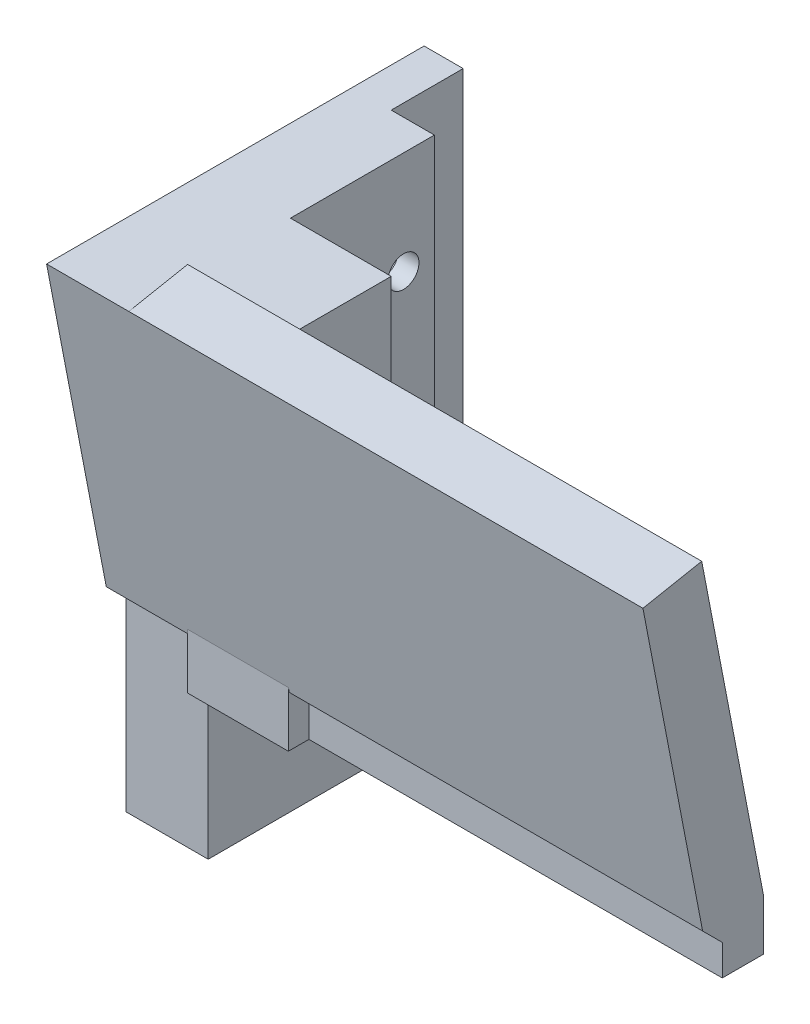
SolidWorks part; units mm, degrees
ref_plane "前视基准面" through (0, 0, 0) normal (0, 0, 1) x (1, 0, 0)
ref_plane "上视基准面" through (0, 0, 0) normal (0, 1, 0) x (1, 0, 0)
ref_plane "右视基准面" through (0, 0, 0) normal (1, 0, 0) x (0, 0, -1)
other "Configuration Table"
sketch "草图1" plane through (0, 0, 0) normal (1, 0, 0) x (0, 0, -1)
  line L0 (0, 0) -> (-10, 0)
  line L1 (-10, 0) -> (-17.7164, 40)
  line L2 (-17.7164, 40) -> (-12, 41.1027)
  line L3 (-12, 41.1027) -> (-6, 10)
  line L4 (-6, 10) -> (0, 10)
  line L5 (0, 10) -> (0, 0)
  dimension "D1" = 10
  dimension "D2" = 6
  dimension "D3" = 10
  dimension "D4" = 6
  dimension "D5" = 40
extrude "凸台-拉伸1" add sketch "草图1" along normal blind 50
sketch "草图2" plane through (0, 0, 0) normal (0, -1, 0) x (1, 0, 0)
  line L4 (0, 10) -> (0, 0)
  line L5 (0, 0) -> (50, 0)
  line L6 (50, 0) -> (50, 10)
  line L7 (50, 10) -> (0, 10)
  line L8 (0, 10) -> (0, 0)
  line L9 (0, 0) -> (50, 0)
  line L10 (50, 0) -> (50, 10)
  line L11 (50, 10) -> (0, 10)
  dimension "D1" = 0
extrude "凸台-拉伸2" add sketch "草图2" along normal blind 10
sketch "草图3" plane through (0, 0, 0) normal (-1, 0, 0) x (0, 0, 1)
  line L1 (0, 10) -> (10, 10)
  line L2 (0, 10) -> (0, -10)
  line L3 (0, -10) -> (10, -10)
  line L4 (10, 10) -> (10, -10)
extrude "凸台-拉伸3" add sketch "草图3" along normal blind 20
sketch "草图4" plane through (0, 10, 0) normal (0, 1, 0) x (1, 0, 0)
  line L1 (-20, 0) -> (0, 0)
  line L2 (-20, 0) -> (-20, -10)
  line L3 (-20, -10) -> (0, -10)
  line L4 (0, 0) -> (0, -10)
extrude "凸台-拉伸4" add sketch "草图4" along normal blind 30
sketch "草图5" plane through (50, 0, 0) normal (1, 0, 0) x (0, 0, -1)
  line L0 (-10, 10) -> (-11.9291, 10)
  line L1 (-17.7164, 40) -> (-10, 0) construction
  line L2 (-11.9291, 10) -> (-10, 0)
  line L3 (-10, 0) -> (-10, 10)
extrude "切除-拉伸1" cut sketch "草图5" against normal up to surface (50 mm away) up to face at (0, 27.9595, 12.4291)
chamfer "倒角1" distance 2 angle 45 1 edges at (25, 10, 10)
sketch "草图9" plane through (0, 0, 10) normal (0, 0, 1) x (1, 0, 0)
  line L0 (-20, 40) -> (-10, 40) construction
  line L1 (-20, 40) -> (0, 40) construction
  line L2 (-10, 40) -> (-10, 30) construction
  line L3 (50, -10) -> (50, 0) construction
  line L4 (50, -10) -> (50, 8) construction
  line L5 (50, 0) -> (30, 0) construction
  circle A0 centre (-10, 30) radius 1.5
  circle A1 centre (30, 0) radius 1.5
  dimension "D3" = 3
  dimension "D5" = 3
  dimension "D1" = 10
  dimension "D2" = 10
  dimension "D4" = 20
extrude "切除-拉伸2" cut sketch "草图9" against normal through all
sketch "草图12" plane through (0, 0, 10) normal (0, 0, 1) x (1, 0, 0)
  line L6 (0, 30.7352) -> (0, 40)
  line L7 (0, 30.7352) -> (0, 40)
  line L8 (0, 40) -> (-20, 40)
  line L9 (50, -10) -> (50, 8)
  line L10 (50, 8) -> (0, 8)
  line L11 (0, 8) -> (0, 30.7352)
  line L15 (50, -10) -> (50, 8)
  line L16 (50, 8) -> (0, 8)
  line L17 (0, 8) -> (0, 30.7352)
  line L19 (0, 40) -> (-20, 40)
  line L20 (-20, 40) -> (-20, -10)
  line L21 (-20, 40) -> (-20, -10)
  line L22 (-20, -10) -> (50, -10)
  line L23 (-20, -10) -> (50, -10)
  dimension "D1" = 0
extrude "切除-拉伸4" cut sketch "草图12" against normal blind 6
sketch "草图13" plane through (0, 8, 0) normal (0, -1, 0) x (1, 0, 0)
  line L0 (50, 4) -> (0, 4) construction
  line L1 (0, 10) -> (4, 10)
  line L2 (0, 10) -> (0, 4)
  line L3 (0, 4) -> (4, 4)
  line L4 (4, 10) -> (4, 4)
  line L6 (50, 10) -> (46, 10)
  line L7 (50, 10) -> (50, 4)
  line L8 (50, 4) -> (46, 4)
  line L9 (46, 10) -> (46, 4)
  dimension "D1" = 4
  dimension "D2" = 4
extrude "凸台-拉伸12" add sketch "草图13" along normal up to surface (18 mm away) up to face at (15, -10, 2)
sketch "草图14" plane through (0, 0, 4) normal (0, 0, 1) x (1, 0, 0)
  line L1 (0, 10) -> (-20, 10)
  line L2 (0, 10) -> (0, -10)
  line L3 (0, -10) -> (-20, -10)
  line L4 (-20, 10) -> (-20, -10)
extrude "凸台-拉伸13" add sketch "草图14" along normal up to surface (6 mm away) up to face at (2, -1, 10)
sketch "草图15" plane through (0, 10, 0) normal (0, 1, 0) x (1, 0, 0)
  line L1 (0, 0) -> (50, 0)
  line L2 (0, 0) -> (0, -6)
  line L3 (0, -6) -> (50, -6)
  line L4 (50, 0) -> (50, -6)
extrude "切除-拉伸5" cut sketch "草图15" against normal up to surface (20 mm away) up to face at (20, -10, 6)
sketch "草图16" plane through (0, -10, 0) normal (0, -1, 0) x (1, 0, 0)
  line L1 (0, 6) -> (4, 6)
  line L2 (0, 6) -> (0, 10)
  line L3 (0, 10) -> (4, 10)
  line L4 (4, 6) -> (4, 10)
  line L5 (50, 6) -> (46, 6)
  line L6 (50, 6) -> (50, 10)
  line L7 (50, 10) -> (46, 10)
  line L8 (46, 6) -> (46, 10)
extrude "切除-拉伸7" cut sketch "草图16" against normal up to surface (18 mm away) up to face at (25, 8, 8)
sketch "草图17" plane through (0, 0, 4) normal (0, 0, 1) x (1, 0, 0)
  line L0 (0, 10) -> (-20, 10) construction
  line L1 (0, 40) -> (-5, 40)
  line L2 (0, 40) -> (0, 10)
  line L3 (0, 10) -> (-5, 10)
  line L4 (-5, 40) -> (-5, 10)
  dimension "D1" = 5
extrude "凸台-拉伸14" add sketch "草图17" along normal up to surface (13.7164 mm away) up to face at (25, 24.9561, 14.8143)
sketch "草图18" plane through (0, 8, 0) normal (0, -1, 0) x (1, 0, 0)
  line L4 (50, 10) -> (0, 10)
  line L5 (0, 10) -> (0, 6)
  line L6 (0, 6) -> (50, 6)
  line L7 (50, 6) -> (50, 10)
  line L8 (50, 10) -> (0, 10)
  line L9 (0, 10) -> (0, 6)
  line L10 (0, 6) -> (50, 6)
  line L11 (50, 6) -> (50, 10)
  dimension "D1" = 0
extrude "凸台-拉伸15" add sketch "草图18" along normal up to surface (18 mm away) up to face at (-10, -10, 5)
sketch "草图19" plane through (0, 0, 10) normal (0, 0, 1) x (1, 0, 0)
  line L0 (-20, -10) -> (-20, 10) construction
  line L1 (-20, 5) -> (40, 5)
  line L2 (-20, 5) -> (-20, -5)
  line L3 (-20, -5) -> (40, -5)
  line L4 (40, 5) -> (40, -5)
  line L5 (50, -10) -> (-20, -10) construction
  line L6 (-5, 10) -> (0, 10) construction
  line L7 (50, -10) -> (50, 8) construction
  dimension "D1" = 5
  dimension "D2" = 5
  dimension "D3" = 10
extrude "切除-拉伸8" cut sketch "草图19" against normal up to surface (6 mm away) up to face at (-8.5, 30, 4)
sketch "草图20" plane through (0, 0, 4) normal (0, 0, 1) x (1, 0, 0)
  line L0 (-10, 30) -> (-10, 0) construction
  circle A0 centre (-10, 0) radius 1.5
  dimension "D1" = 3
extrude "切除-拉伸9" cut sketch "草图20" against normal up to surface (4 mm away) up to face at (-8.5, 30, 0)
chamfer "倒角2" distance 2 angle 45 1 edges at (-2.5, 10, 10)
sketch "草图21" plane through (0, 0, 10) normal (0, 0, 1) x (1, 0, 0)
  line L1 (-5, 40) -> (-20, 40)
  line L2 (-5, 40) -> (-5, -10)
  line L3 (-5, -10) -> (-20, -10)
  line L4 (-20, 40) -> (-20, -10)
extrude "切除-拉伸10" cut sketch "草图21" against normal up to surface (10 mm away) up to face at (-8.5, 0, 0)
sketch "草图22" plane through (0, 0, 0) normal (0, 0, -1) x (-1, 0, 0)
  line L4 (0, -10) -> (5, -10)
  line L5 (5, -10) -> (5, 40)
  line L6 (5, 40) -> (0, 40)
  line L7 (0, 40) -> (0, -10)
  line L8 (0, -10) -> (5, -10)
  line L9 (5, -10) -> (5, 40)
  line L10 (5, 40) -> (0, 40)
  line L11 (0, 40) -> (0, -10)
  dimension "D1" = 0
extrude "凸台-拉伸16" add sketch "草图22" along normal blind 19
sketch "草图23" plane through (0, 0, 0) normal (1, 0, 0) x (0, 0, -1)
  line L0 (19, -10) -> (-6, -10) construction
  line L1 (19, 40) -> (12, 40)
  line L2 (19, 40) -> (19, -10)
  line L3 (19, -10) -> (12, -10)
  line L4 (12, 40) -> (12, -10)
  dimension "D1" = 7
extrude "切除-拉伸11" cut sketch "草图23" against normal blind 4.2
sketch "草图24" plane through (-5, 0, 0) normal (-1, 0, 0) x (0, 0, 1)
  line L10 (17.7164, 40) -> (-19, 40)
  line L11 (-19, 40) -> (-19, -10)
  line L12 (-19, -10) -> (10, -10)
  line L13 (10, -10) -> (10, -5)
  line L14 (10, -5) -> (4, -5)
  line L15 (4, -5) -> (4, 5)
  line L16 (4, 5) -> (10, 5)
  line L17 (10, 5) -> (10, 8)
  line L18 (10, 8) -> (11.9121, 9.9121)
  line L19 (11.9121, 9.9121) -> (17.7164, 40)
  line L20 (17.7164, 40) -> (-19, 40)
  line L21 (-19, 40) -> (-19, -10)
  line L22 (-19, -10) -> (10, -10)
  line L23 (10, -10) -> (10, -5)
  line L24 (10, -5) -> (4, -5)
  line L25 (4, -5) -> (4, 5)
  line L26 (4, 5) -> (10, 5)
  line L27 (10, 5) -> (10, 8)
  line L28 (10, 8) -> (11.9121, 9.9121)
  line L29 (11.9121, 9.9121) -> (17.7164, 40)
  dimension "D1" = 0
extrude "凸台-拉伸17" add sketch "草图24" along normal blind 3
sketch "草图25" plane through (-8, 0, 0) normal (-1, 0, 0) x (0, 0, 1)
  line L0 (-19, 40) -> (-9, 40) construction
  line L1 (17.7164, 40) -> (-19, 40) construction
  line L2 (-9, 40) -> (-9, 30) construction
  line L3 (-9, 30) -> (-9, 0) construction
  circle A0 centre (-9, 30) radius 1.5
  circle A1 centre (-9, 0) radius 1.5
  dimension "D3" = 3
  dimension "D4" = 3
  dimension "D1" = 10
  dimension "D2" = 30
  dimension "D5" = 10
extrude "切除-拉伸12" cut sketch "草图25" against normal up to surface (8 mm away) up to face at (0, 7.7778, 2.1986)
sketch "草图26" plane through (-8, 0, 0) normal (-1, 0, 0) x (0, 0, 1)
  circle A0 centre (-9, 30) radius 2.9
  circle A1 centre (-9, 0) radius 2.9
  dimension "D1" = 5.8
  dimension "D2" = 5.8
extrude "切除-拉伸13" cut sketch "草图26" against normal offset from surface (6 mm away) 2 up to face at (0, 30, -7.5)
sketch "草图27" plane through (40, 0, 0) normal (-1, 0, 0) x (0, 0, 1)
  line L4 (6, -5) -> (10, -5)
  line L5 (10, -5) -> (10, 5)
  line L6 (10, 5) -> (6, 5)
  line L7 (6, 5) -> (6, -5)
  line L8 (6, -5) -> (10, -5)
  line L9 (10, -5) -> (10, 5)
  line L10 (10, 5) -> (6, 5)
  line L11 (6, 5) -> (6, -5)
  dimension "D1" = 0
extrude "切除-拉伸14" cut sketch "草图27" against normal up to next
sketch "草图29" plane through (0, 0, 4) normal (0, 0, 1) x (1, 0, 0)
  line L4 (0, 5) -> (-8, 5)
  line L5 (-8, 5) -> (-8, -5)
  line L6 (-8, -5) -> (0, -5)
  line L7 (0, -5) -> (0, 5)
  line L8 (0, 5) -> (-8, 5)
  line L9 (-8, 5) -> (-8, -5)
  line L10 (-8, -5) -> (0, -5)
  line L11 (0, -5) -> (0, 5)
  dimension "D1" = 0
extrude "凸台-拉伸18" add sketch "草图29" along normal up to surface (6 mm away) up to face at (21, -7.5, 10)
sketch "草图30" plane through (0, 0, 10) normal (0, 0, 1) x (1, 0, 0)
  line L1 (0, -5) -> (50, -5)
  line L2 (0, -5) -> (0, -10)
  line L3 (0, -10) -> (50, -10)
  line L4 (50, -5) -> (50, -10)
extrude "切除-拉伸15" cut sketch "草图30" against normal up to surface (4 mm away) up to face at (25, 7.5, 6)
sketch "草图31" plane through (0, 40, 0) normal (0, 1, 0) x (1, 0, 0)
  line L0 (0, -11.7873) -> (0, 12) construction
  line L1 (0, -2) -> (9.8, -2)
  line L2 (0, -2) -> (0, -12)
  line L3 (0, -12) -> (9.8, -12)
  line L4 (9.8, -2) -> (9.8, -12)
  line L5 (50, -12) -> (0, -12) construction
  line L6 (-8, 19) -> (-4.2, 19) construction
  dimension "D1" = 21
  dimension "D2" = 9.8
extrude "凸台-拉伸19" add sketch "草图31" against normal up to surface (35 mm away) up to face at (25, 5, 8)
